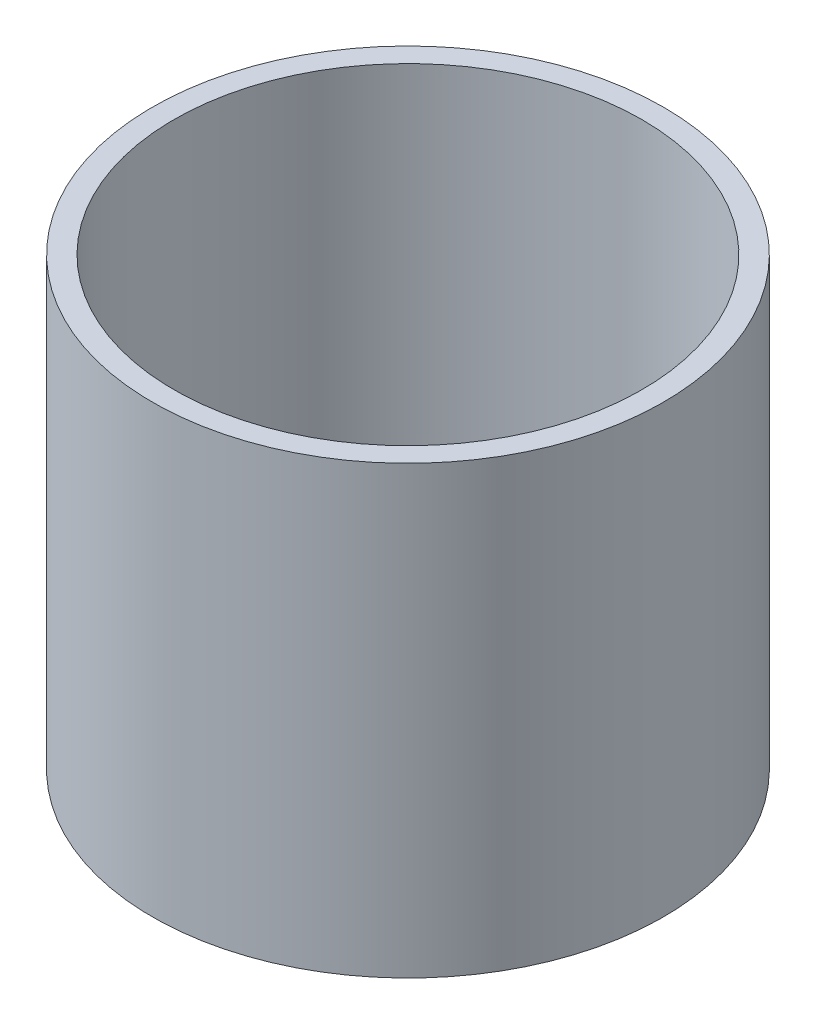
SolidWorks part; units mm, degrees
material "7075-T6 (SN)"
ref_plane "Front Plane" through (0, 0, 0) normal (0, 0, 1) x (1, 0, 0)
ref_plane "Top Plane" through (0, 0, 0) normal (0, 1, 0) x (1, 0, 0)
ref_plane "Right Plane" through (0, 0, 0) normal (1, 0, 0) x (0, 0, -1)
sketch "Sketch1" plane through (0, 0, 0) normal (0, 1, 0) x (1, 0, 0)
  circle A0 centre (0, 0) radius 43.68
  circle A1 centre (0, 0) radius 40
  dimension "D1" = 87.36
  dimension "D2" = 80
extrude "Boss-Extrude1" add sketch "Sketch1" along normal blind 76.2
